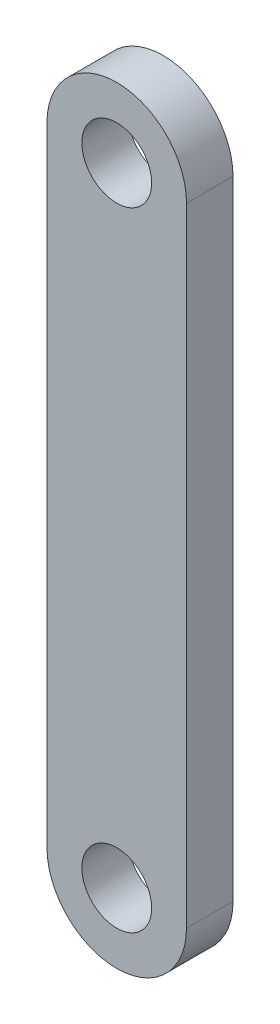
SolidWorks part; units mm, degrees
ref_plane "Front Plane" through (0, 0, 0) normal (0, 0, 1) x (1, 0, 0)
ref_plane "Top Plane" through (0, 0, 0) normal (0, 1, 0) x (1, 0, 0)
ref_plane "Right Plane" through (0, 0, 0) normal (1, 0, 0) x (0, 0, -1)
sketch "Sketch1" plane through (0, 0, 0) normal (0, 0, 1) x (1, 0, 0)
  line L0 (-15, 135) -> (-15, 0)
  line L1 (15, 135) -> (15, 0)
  circle A0 centre (0, 135) radius 7.5
  circle A1 centre (0, 0) radius 7.5
  arc A2 (15, 135) -> (-15, 135) centre (0, 135) ccw
  arc A3 (-15, 0) -> (15, 0) centre (0, 0) ccw
  dimension "D2" = 15
  dimension "D3" = 30
  dimension "D1" = 135
extrude "Boss-Extrude1" add sketch "Sketch1" along normal blind 10
